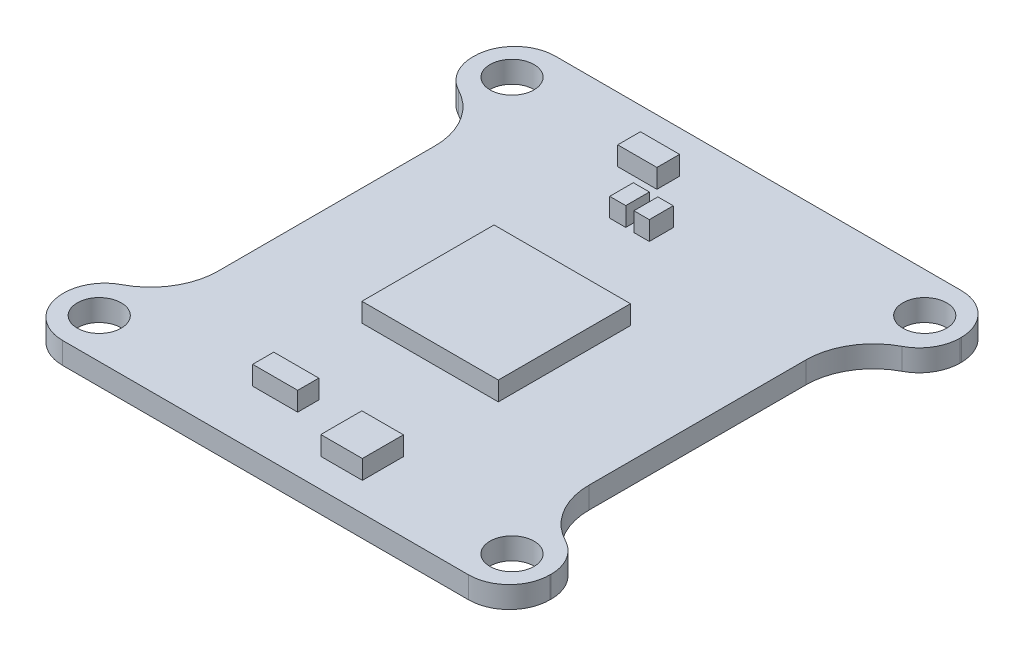
SolidWorks part; units mm, degrees
ref_plane "Front Plane" through (0, 0, 0) normal (0, 0, 1) x (1, 0, 0)
ref_plane "Top Plane" through (0, 0, 0) normal (0, 1, 0) x (1, 0, 0)
ref_plane "Right Plane" through (0, 0, 0) normal (1, 0, 0) x (0, 0, -1)
sketch "Sketch1" plane through (0, 0, 0) normal (0, 1, 0) x (1, 0, 0)
  line L0 (0, 18.2) -> (0, -18.2) construction
  line L1 (-18, 18.2) -> (18, 18.2)
  line L2 (-18, 18.2) -> (-18, -18.2)
  line L3 (-18, -18.2) -> (18, -18.2)
  line L4 (18, 18.2) -> (18, -18.2)
  line L5 (-18, 18.2) -> (18, -18.2) construction
  line L6 (-18, -18.2) -> (18, 18.2) construction
  line L7 (13.7, 18.2) -> (-13.7, 18.2)
  line L8 (13.7, 18.2) -> (13.7, -18.2)
  line L9 (13.7, -18.2) -> (-13.7, -18.2)
  line L10 (-13.7, 18.2) -> (-13.7, -18.2)
  line L11 (13.7, 18.2) -> (-13.7, -18.2) construction
  line L12 (13.7, -18.2) -> (-13.7, 18.2) construction
  line L13 (-18, 0) -> (18, 0) construction
  line L15 (18, 12.1) -> (-18, 12.1)
  line L16 (18, 12.1) -> (18, -12.1)
  line L17 (18, -12.1) -> (-18, -12.1)
  line L18 (-18, 12.1) -> (-18, -12.1)
  line L19 (18, 12.1) -> (-18, -12.1) construction
  line L20 (18, -12.1) -> (-18, 12.1) construction
  circle A0 centre (-15.25, 15.25) radius 1.625
  circle A1 centre (15.25, 15.25) radius 1.625
  circle A2 centre (15.25, -15.25) radius 1.625
  circle A3 centre (-15.25, -15.25) radius 1.625
  point P0 (0, 0)
  point P5 (0, 0)
  point P23 (0, 0)
  dimension "D4" = 3.25
  dimension "D1" = 36.4
  dimension "D2" = 36
  dimension "D3" = 27.4
  dimension "D5" = 30.5
  dimension "D6" = 30.5
  dimension "D7" = 24.2
extrude "PCB" add sketch "Sketch1" along normal blind 1.6 contours L15 L8 L1 L10 | L17 L8 L15 L10 | L4 L17 L8 L3 A2 | L8 L17 L10 L3 | L10 L17 L2 L3 A3 | L15 L4 L1 L8 A1 | L15 L10 L1 L2 A0 region at (-15.85, 0, -18.1254) region at (0, 0, -15.1499) region at (15.85, 0, -18.1254) region at (-15.85, 0, 12.1746) region at (0, 0, 0) region at (0, 0, 15.1499) region at (15.85, 0, 12.1746)
sketch "Sketch2" plane through (0, 1.6, 0) normal (0, 1, 0) x (1, 0, 0)
  line L1 (-5.0578, -6.0345) -> (5.023, -6.0345)
  line L2 (-5.0578, -6.0345) -> (-5.0578, 3.7323)
  line L3 (-5.0578, 3.7323) -> (5.023, 3.7323)
  line L4 (5.023, -6.0345) -> (5.023, 3.7323)
  line L5 (1.9534, -13.0458) -> (5.023, -13.0458)
  line L6 (1.9534, -13.0458) -> (1.9534, -16.0805)
  line L7 (1.9534, -16.0805) -> (5.023, -16.0805)
  line L8 (5.023, -13.0458) -> (5.023, -16.0805)
  line L9 (-5.616, 15.1038) -> (-2.7208, 15.1038)
  line L10 (-5.616, 15.1038) -> (-5.616, 13.4294)
  line L11 (-5.616, 13.4294) -> (-2.7208, 13.4294)
  line L12 (-2.7208, 15.1038) -> (-2.7208, 13.4294)
  line L13 (-2.6161, 11.5807) -> (-1.4301, 11.5807)
  line L14 (-2.6161, 11.5807) -> (-2.6161, 9.8366)
  line L15 (-2.6161, 9.8366) -> (-1.4301, 9.8366)
  line L16 (-1.4301, 11.5807) -> (-1.4301, 9.8366)
  line L17 (-0.8023, 11.5807) -> (0.3353, 11.5807)
  line L18 (-0.8023, 11.5807) -> (-0.8023, 9.8089)
  line L19 (-0.8023, 9.8089) -> (0.3353, 9.8089)
  line L20 (0.3353, 11.5807) -> (0.3353, 9.8089)
  line L21 (-1.7319, -12.5448) -> (-5.0578, -12.5448)
  line L22 (-1.7319, -12.5448) -> (-1.7319, -14.1049)
  line L23 (-1.7319, -14.1049) -> (-5.0578, -14.1049)
  line L24 (-5.0578, -12.5448) -> (-5.0578, -14.1049)
extrude "Top components" add sketch "Sketch2" along normal blind 1.4
fillet "Fillet1" radius 3 8 edges at (-18, 0.8, 12.1) (-18, 0.8, -12.1) (18, 0.8, -12.1) (18, 0.8, 12.1) (18, 0.8, 18.2) (-18, 0.8, 18.2) (-18, 0.8, -18.2) (18, 0.8, -18.2)
fillet "Fillet2" radius 5 4 edges at (13.7, 0.8, -12.1) (13.7, 0.8, 12.1) (-13.7, 0.8, 12.1) (-13.7, 0.8, -12.1)
sketch "Sketch3" plane through (0, 0, 0) normal (0, -1, 0) x (1, 0, 0)
  line L1 (-9.9064, -12.8365) -> (-6.7322, -12.8365)
  line L2 (-9.9064, -12.8365) -> (-9.9064, -15.8014)
  line L3 (-9.9064, -15.8014) -> (-6.7322, -15.8014)
  line L4 (-6.7322, -12.8365) -> (-6.7322, -15.8014)
  line L5 (-5.8601, -13.3597) -> (-2.7557, -13.3597)
  line L6 (-5.8601, -13.3597) -> (-5.8601, -14.8945)
  line L7 (-5.8601, -14.8945) -> (-2.7557, -14.8945)
  line L8 (-2.7557, -13.3597) -> (-2.7557, -14.8945)
  line L9 (2.1627, 10.325) -> (5.1625, 10.325)
  line L10 (2.1627, 10.325) -> (2.1627, 8.7553)
  line L11 (2.1627, 8.7553) -> (5.1625, 8.7553)
  line L12 (5.1625, 10.325) -> (5.1625, 8.7553)
  line L13 (-4.7788, 10.918) -> (-3.5231, 10.918)
  line L14 (-4.7788, 10.918) -> (-4.7788, 8.0228)
  line L15 (-4.7788, 8.0228) -> (-3.5231, 8.0228)
  line L16 (-3.5231, 10.918) -> (-3.5231, 8.0228)
  line L17 (-0.9767, -13.3597) -> (-2.1278, -13.3597)
  line L18 (-0.9767, -13.3597) -> (-0.9767, -15.4177)
  line L19 (-0.9767, -15.4177) -> (-2.1278, -15.4177)
  line L20 (-2.1278, -13.3597) -> (-2.1278, -15.4177)
extrude "Boss-Extrude3" add sketch "Sketch3" along normal blind 1.4
